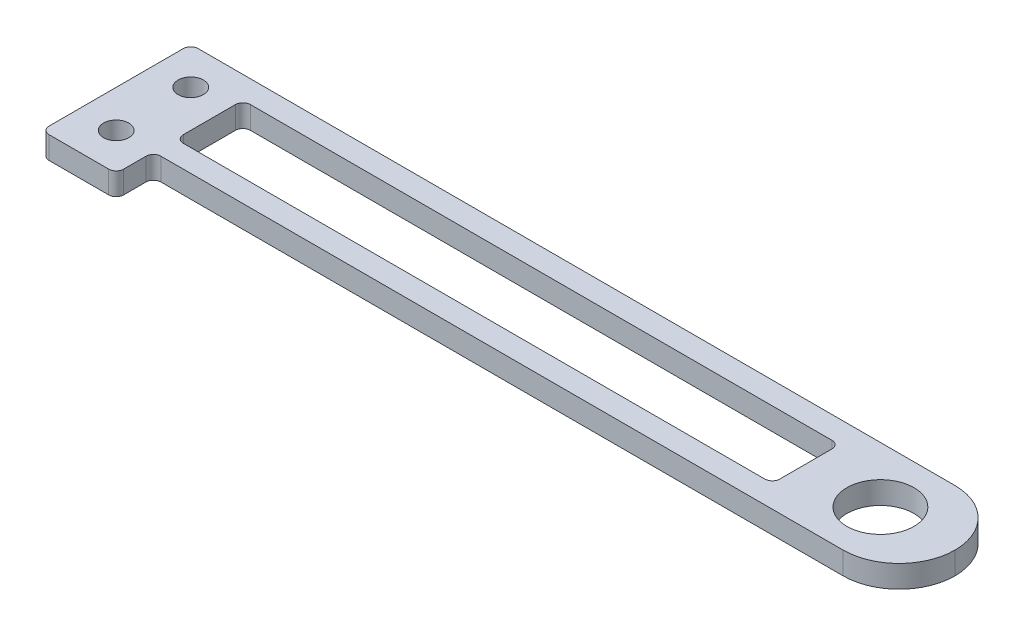
SolidWorks part; units mm, degrees
ref_plane "Front Plane" through (0, 0, 0) normal (0, 0, 1) x (1, 0, 0)
ref_plane "Top Plane" through (0, 0, 0) normal (0, 1, 0) x (1, 0, 0)
ref_plane "Right Plane" through (0, 0, 0) normal (1, 0, 0) x (0, 0, -1)
sketch "Sketch1" plane through (0, 0, 0) normal (0, 1, 0) x (1, 0, 0)
  line L0 (0, 0) -> (0, 20)
  line L1 (0, 20) -> (110, 20)
  line L2 (110, 20) -> (110, 5)
  line L3 (110, 5) -> (10, 5)
  line L4 (10, 5) -> (10, 0)
  line L5 (10, 0) -> (0, 0)
  dimension "D1" = 20
  dimension "D2" = 110
  dimension "D3" = 15
  dimension "D4" = 10
extrude "Boss-Extrude1" add sketch "Sketch1" along normal blind 3
hole_wizard "M8 Clearance Hole1" positions "3DSketch2" profile "Sketch4" hole size "M8" standard "ISO" end condition through all
sketch3d "3DSketch2"
  line L0 (110, 3, -5) -> (110, 3, -20) construction
  line L1 (110, 3, -20) -> (0, 3, -20) construction
  point P0 (100, 3, -12.5)
  dimension "D1" = 10
  dimension "D2" = 7.5
sketch "Sketch4" plane through (100, 3, -12.5) normal (1, 0, 0) x (0, 0, 1)
  line L0 (0, 0) -> (0, 3)
  line L1 (0, 3) -> (4.5, 3)
  line L2 (4.5, 3) -> (4.5, 0)
  line L5 (4.5, 0) -> (0, 0)
  line L11 (0, -6.35) -> (0, 107.95) construction
  dimension "Thru Hole Dia." = 9
  dimension "Thru Hole Depth" = 3
hole_wizard "M3 Clearance Hole1" positions "3DSketch3" profile "Sketch5" hole size "M3" standard "ISO" end condition through all
sketch3d "3DSketch3"
  line L0 (0, 3, -20) -> (0, 3, 0) construction
  line L1 (0, 3, 0) -> (10, 3, 0) construction
  line L2 (110, 3, -20) -> (0, 3, -20) construction
  point P0 (5, 3, -15)
  point P2 (5, 3, -5)
  dimension "D1" = 5
  dimension "D2" = 5
  dimension "D3" = 5
  dimension "D4" = 5
sketch "Sketch5" plane through (5, 3, -15) normal (1, 0, 0) x (0, 0, 1)
  line L0 (0, 0) -> (0, 3)
  line L1 (0, 3) -> (1.7, 3)
  line L2 (1.7, 3) -> (1.7, 0)
  line L5 (1.7, 0) -> (0, 0)
  line L11 (0, -6.35) -> (0, 107.95) construction
  dimension "Thru Hole Dia." = 3.4
  dimension "Thru Hole Depth" = 3
fillet "Fillet1" radius 1 4 edges at (0, 1.5, 0) (10, 1.5, -5) (0, 1.5, -20) (10, 1.5, 0)
fillet "Fillet2" radius 7.5 2 edges at (110, 1.5, -20) (110, 1.5, -5)
sketch "Sketch6" plane through (0, 3, 0) normal (0, 1, 0) x (1, 0, 0)
  line L0 (0, 19) -> (0, 1) construction
  line L1 (10, 17) -> (90, 17)
  line L2 (10, 17) -> (10, 8)
  line L3 (10, 8) -> (90, 8)
  line L4 (90, 17) -> (90, 8)
  line L6 (11, 5) -> (102.5, 5) construction
  dimension "D1" = 20
  dimension "D2" = 10
  dimension "D3" = 9
  dimension "D4" = 3
extrude "Cut-Extrude1" cut sketch "Sketch6" against normal through all
fillet "Fillet3" radius 1 4 edges at (90, 1.5, -8) (90, 1.5, -17) (10, 1.5, -8) (10, 1.5, -17)
